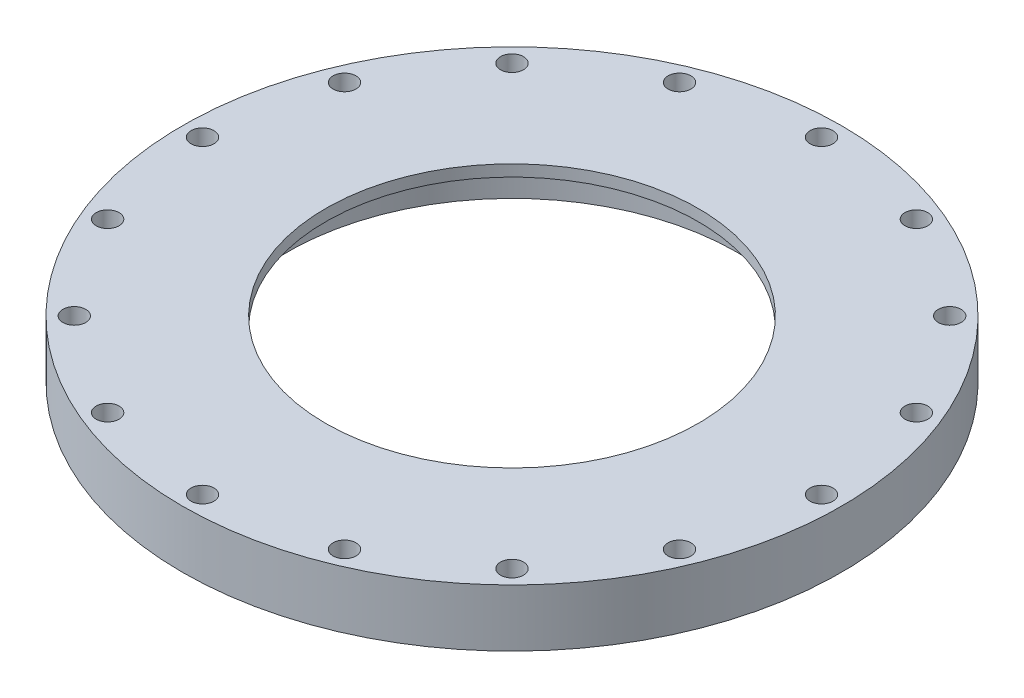
SolidWorks part; units mm, degrees
ref_plane "Front Plane" through (0, 0, 0) normal (0, 0, 1) x (1, 0, 0)
ref_plane "Top Plane" through (0, 0, 0) normal (0, 1, 0) x (1, 0, 0)
ref_plane "Right Plane" through (0, 0, 0) normal (1, 0, 0) x (0, 0, -1)
sketch "Sketch1" plane through (0, 0, 0) normal (0, 1, 0) x (1, 0, 0)
  circle A0 centre (0, 0) radius 57.5
  circle A1 centre (0, 0) radius 39.25
  dimension "D1" = 78.5
  dimension "D2" = 115
extrude "Boss-Extrude1" add sketch "Sketch1" along normal blind 8
sketch "Sketch3" plane through (0, 8, 0) normal (0, 1, 0) x (1, 0, 0)
  circle A0 centre (0, 0) radius 57.5
  circle A1 centre (0, 0) radius 32.5
  dimension "D1" = 65
extrude "Boss-Extrude2" add sketch "Sketch3" along normal blind 2
sketch "Sketch2" plane through (0, 10, 0) normal (0, 1, 0) x (1, 0, 0)
  circle A0 centre (0, 0) radius 54 construction
  circle A1 centre (0, 54) radius 2
  circle A2 centre (20.6649, 49.8895) radius 2
  circle A3 centre (38.1838, 38.1838) radius 2
  circle A4 centre (49.8895, 20.6649) radius 2
  circle A5 centre (54, 0) radius 2
  circle A6 centre (49.8895, -20.6649) radius 2
  circle A7 centre (38.1838, -38.1838) radius 2
  circle A8 centre (20.6649, -49.8895) radius 2
  circle A9 centre (0, -54) radius 2
  circle A10 centre (-20.6649, -49.8895) radius 2
  circle A11 centre (-38.1838, -38.1838) radius 2
  circle A12 centre (-49.8895, -20.6649) radius 2
  circle A13 centre (-54, 0) radius 2
  circle A14 centre (-49.8895, 20.6649) radius 2
  circle A15 centre (-38.1838, 38.1838) radius 2
  circle A16 centre (-20.6649, 49.8895) radius 2
  point P37 (0, 0)
  dimension "D1" = 108
  dimension "D2" = 4
  dimension "D3" = 16
extrude "Cut-Extrude1" cut sketch "Sketch2" against normal blind 25
